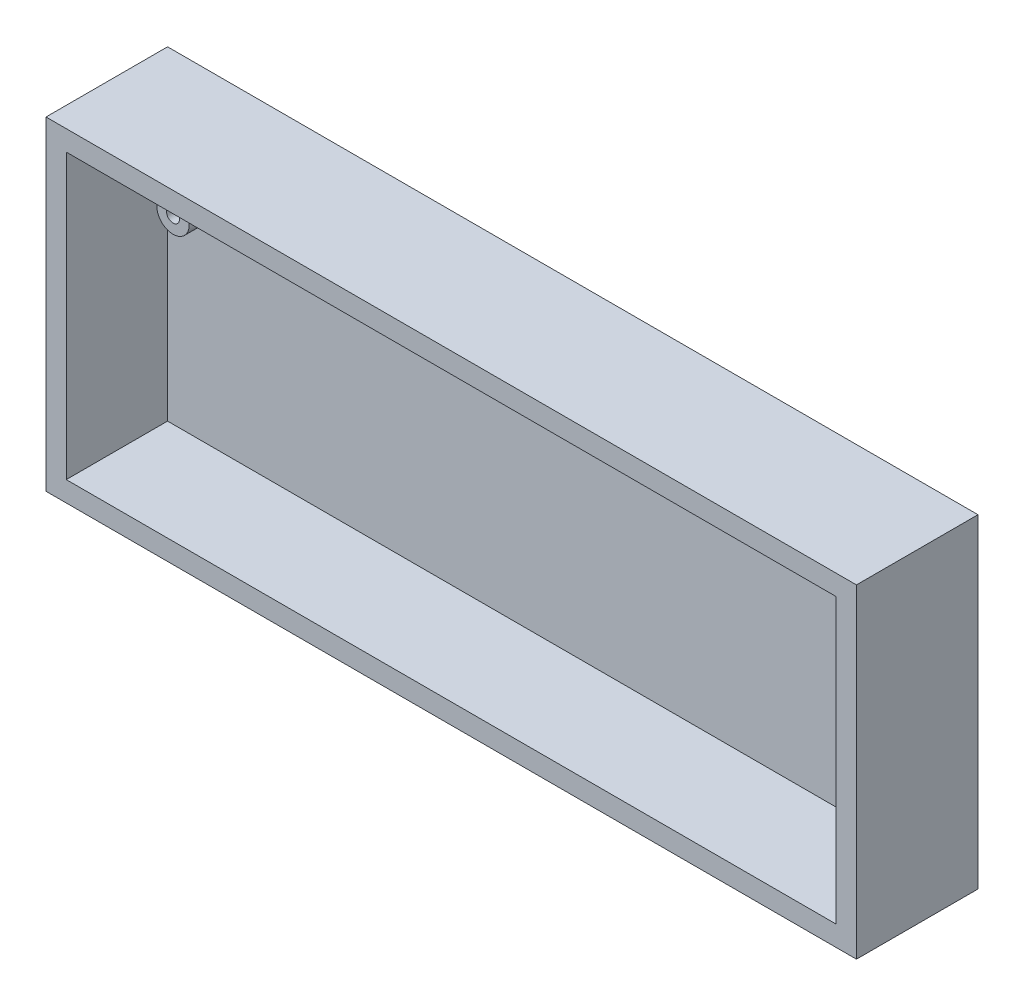
SolidWorks part; units mm, degrees
ref_plane "Front Plane" through (0, 0, 0) normal (0, 0, 1) x (1, 0, 0)
ref_plane "Top Plane" through (0, 0, 0) normal (0, 1, 0) x (1, 0, 0)
ref_plane "Right Plane" through (0, 0, 0) normal (1, 0, 0) x (0, 0, -1)
sketch "Sketch1" plane through (0, 0, 0) normal (0, 0, 1) x (1, 0, 0)
  line L1 (-96.8278, 62.2356) -> (103.1722, 62.2356)
  line L2 (-96.8278, 62.2356) -> (-96.8278, -17.7644)
  line L3 (-96.8278, -17.7644) -> (103.1722, -17.7644)
  line L4 (103.1722, 62.2356) -> (103.1722, -17.7644)
  dimension "D1" = 200
  dimension "D2" = 80
extrude "Boss-Extrude1" add sketch "Sketch1" along normal blind 60
shell "Shell1" thickness 5
sketch "Sketch5" plane through (0, 0, 5) normal (0, 0, 1) x (1, 0, 0)
  line L1 (98.1722, 57.2356) -> (-91.8278, 57.2356) construction
  line L2 (-91.8278, 57.2356) -> (-91.8278, -12.7644) construction
  circle A0 centre (-77.4778, 44.8406) radius 4
  dimension "D1" = 8
  dimension "D2" = 14.35
  dimension "D3" = 12.395
sketch "Sketch3" plane through (0, 0, 60) normal (0, 0, 1) x (1, 0, 0)
  line L1 (-106.5133, 69.14) -> (112.8577, 69.14)
  line L2 (-106.5133, 69.14) -> (-106.5133, -25.4988)
  line L3 (-106.5133, -25.4988) -> (112.8577, -25.4988)
  line L4 (112.8577, 69.14) -> (112.8577, -25.4988)
extrude "Cut-Extrude3" cut sketch "Sketch3" against normal blind 30
extrude "Boss-Extrude2" add sketch "Sketch5" along normal blind 13
sketch "Sketch6" plane through (0, 0, 18) normal (0, 0, 1) x (1, 0, 0)
  circle A0 centre (-77.4778, 44.8406) radius 1.6
  dimension "D1" = 3.2
extrude "Cut-Extrude5" cut sketch "Sketch6" against normal up to surface (18 mm away) up to face at (3.1722, 22.2356, 0)
